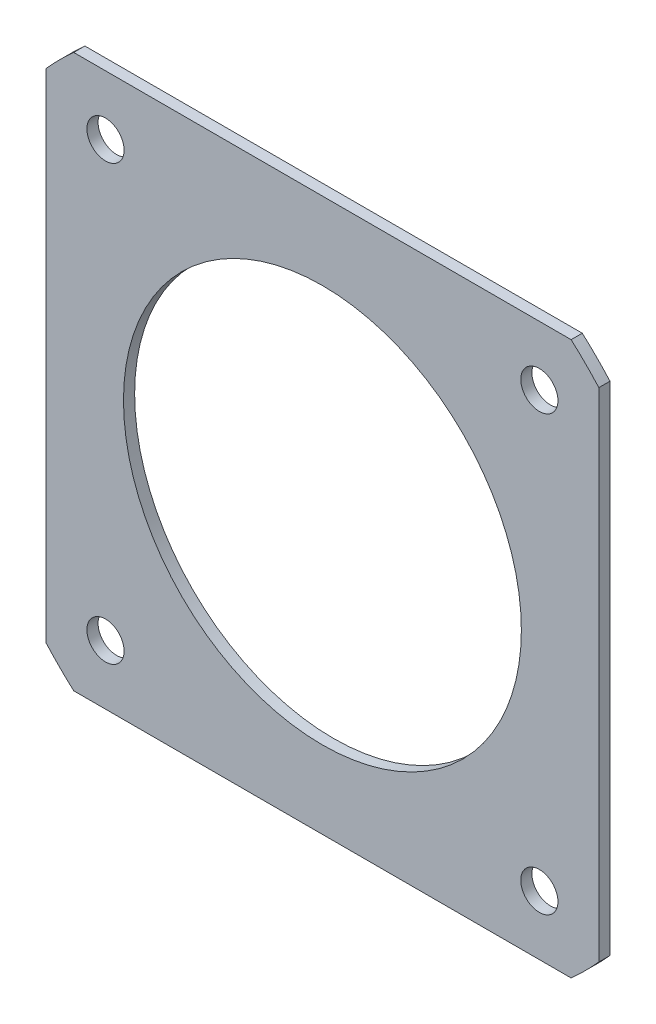
SolidWorks part; units mm, degrees
material "AISI 1020"
ref_plane "Спереди" through (0, 0, 0) normal (0, 0, 1) x (1, 0, 0)
ref_plane "Сверху" through (0, 0, 0) normal (0, 1, 0) x (1, 0, 0)
ref_plane "Справа" through (0, 0, 0) normal (1, 0, 0) x (0, 0, -1)
sketch "Эскиз1" plane through (0, 0, 0) normal (0, 0, 1) x (1, 0, 0)
  line L0 (66.8888, 60.6637) -> (-66.8888, 60.6637) construction
  line L1 (74.3363, 201.8888) -> (74.3363, 68.1112) construction
  line L2 (-66.8888, 209.3363) -> (66.8888, 209.3363) construction
  line L3 (66.8888, 60.6637) -> (-66.8888, 60.6637)
  line L4 (74.3363, 201.8888) -> (74.3363, 68.1112)
  line L5 (-66.8888, 209.3363) -> (66.8888, 209.3363)
  line L6 (-74.3363, 68.1112) -> (-74.3363, 201.8888) construction
  line L7 (-74.3363, 68.1112) -> (-74.3363, 201.8888)
  circle A0 centre (0, 135) radius 53.5 construction
  circle A1 centre (0, 135) radius 53.5
  circle A2 centre (-58.3363, 76.6637) radius 5 construction
  circle A3 centre (58.3363, 76.6637) radius 5 construction
  circle A4 centre (58.3363, 193.3363) radius 5 construction
  circle A5 centre (-58.3363, 193.3363) radius 5 construction
  circle A6 centre (-58.3363, 76.6637) radius 5
  circle A7 centre (58.3363, 76.6637) radius 5
  circle A8 centre (58.3363, 193.3363) radius 5
  circle A9 centre (-58.3363, 193.3363) radius 5
  arc A10 (-74.3363, 68.1112) -> (-66.8888, 60.6637) centre (0, 135) ccw construction
  arc A11 (66.8888, 60.6637) -> (74.3363, 68.1112) centre (0, 135) ccw construction
  arc A12 (74.3363, 201.8888) -> (66.8888, 209.3363) centre (0, 135) ccw construction
  arc A13 (-66.8888, 209.3363) -> (-74.3363, 201.8888) centre (0, 135) ccw construction
  arc A14 (-74.3363, 68.1112) -> (-66.8888, 60.6637) centre (0, 135) ccw
  arc A15 (66.8888, 60.6637) -> (74.3363, 68.1112) centre (0, 135) ccw
  arc A16 (74.3363, 201.8888) -> (66.8888, 209.3363) centre (0, 135) ccw
  arc A17 (-66.8888, 209.3363) -> (-74.3363, 201.8888) centre (0, 135) ccw
base flange "Базовая кромка1" sketch "Эскиз1" thickness 3 reverse thickness direction yes parameters "D1"=0.7366
sketch "Сгиб-Линии1" [suppressed] plane through (0, 0, 0) normal (0, 1, 0) x (1, 0, 0)
sketch "Граничная рамка1" [suppressed] plane through (0, 0, 0) normal (0, 1, 0) x (1, 0, 0)
sheet metal parameters "Листовой металл3" thickness 3 parameters "D1"=0.7366
flat pattern "Развертка3" [suppressed]
sketch "Сгиб-Линии2" plane through (0, 0, 0) normal (0, 1, 0) x (1, 0, 0)
sketch3d "Граничная рамка2" [suppressed]
  line L0 (-74.3363, 74.3363, 0) -> (-74.3363, -74.3363, 0) construction
  line L1 (74.3363, 74.3363, 0) -> (74.3363, -74.3363, 0) construction
  line L2 (-74.3363, 74.3363, 0) -> (74.3363, 74.3363, 0) construction
  line L3 (-74.3363, -74.3363, 0) -> (74.3363, -74.3363, 0) construction
